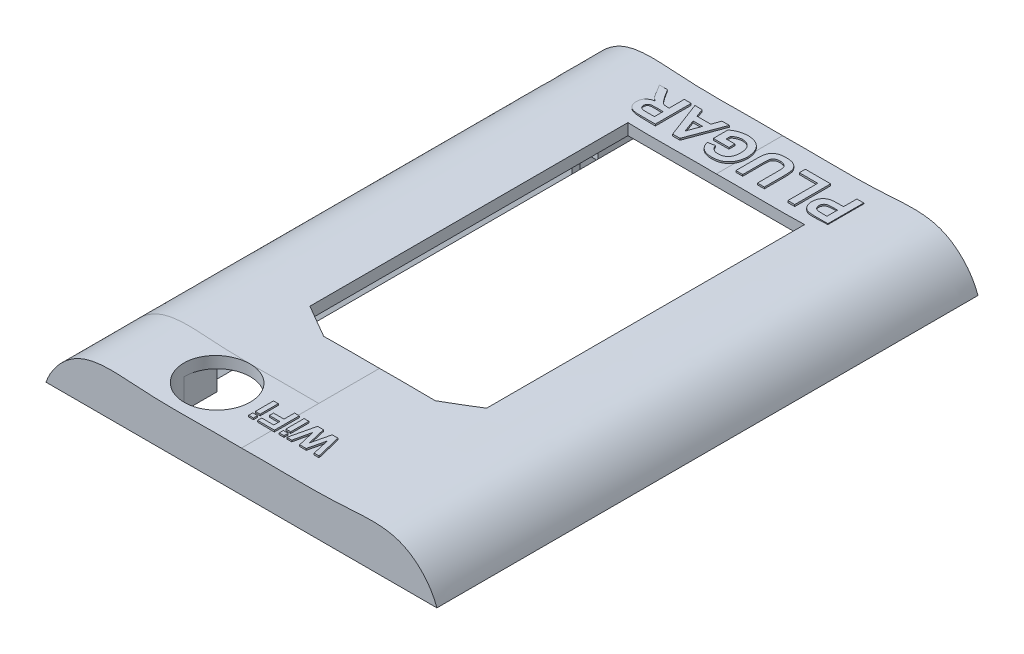
SolidWorks part; units mm, degrees
other "Câmera1"
ref_plane "Plano frontal" through (0, 0, 0) normal (0, 0, 1) x (1, 0, 0)
ref_plane "Plano superior" through (0, 0, 0) normal (0, 1, 0) x (1, 0, 0)
ref_plane "Plano direito" through (0, 0, 0) normal (1, 0, 0) x (0, 0, -1)
sketch "Forma Principal" plane through (0, 0, 0) normal (0, 0, 1) x (1, 0, 0)
  line L0 (20.4, -12.0302) -> (20.4, -9.6302)
  line L1 (0, 6.1527) -> (0, -15) construction
  line L2 (-20.4, -15) -> (-18.9151, -13.5151)
  line L3 (-35.4, -15) -> (-20.4, -15)
  line L4 (-20.4, -9.6302) -> (20.4, -9.6302)
  line L5 (-18.9151, -13.5151) -> (-20.4, -12.0302)
  line L6 (-20.4, -12.0302) -> (-20.4, -9.6302)
  line L7 (18.9151, -13.5151) -> (20.4, -12.0302)
  line L8 (35.4, -15) -> (20.4, -15)
  line L9 (20.4, -15) -> (18.9151, -13.5151)
  spline S0 degree 3 poles (-35.4, -15) (-34.3652, -12.0385) (-29.3659, -6.48) (-20.6106, -7.4076) (-11.0454, -7.778) (-4.641, -7.544) (0, -7.6302) knots 0 0 0 0 0.248558 0.508028 0.637571 1 1 1 1
  spline S1 degree 3 poles (35.4, -15) (34.3652, -12.0385) (29.3659, -6.48) (20.6106, -7.4076) (11.0454, -7.778) (4.641, -7.544) (0, -7.6302) knots 0 0 0 0 0.248558 0.508028 0.637571 1 1 1 1
  point P0 (0, 0)
  point P25 (0, -9.6302)
  dimension "D6" = 10
  dimension "D7" = 19
  dimension "D9" = 4
  dimension "D10" = 2
  dimension "D12" = 2.2
  dimension "D13" = 2
  dimension "D8" = 14
  dimension "D3" = 38.793
  dimension "D2" = 20.4
  dimension "D4" = 4
  dimension "D5" = 15
  dimension "D11" = 2
  dimension "D14" = 2.1
  dimension "D15" = 2.1
  dimension "D16" = 45
  dimension "D17" = 15
  dimension "D18" = 7
  dimension "D19" = 2.4
extrude "Corpo da Tampa" add sketch "Forma Principal" along normal blind 84
sketch "Esboço4" plane through (0, 0, 84) normal (0, 0, 1) x (1, 0, 0)
  line L1 (0, -7.6302) -> (0, -15) construction
  line L2 (-35.4, -15) -> (35.4, -15)
  spline S0 degree 3 poles (-35.4, -15) (-34.3652, -12.0385) (-29.3659, -6.48) (-20.6106, -7.4076) (-11.0454, -7.778) (-4.641, -7.544) (0, -7.6302) knots 0 0 0 0 0.248558 0.508028 0.637571 1 1 1 1
  spline S1 degree 3 poles (35.4, -15) (34.3652, -12.0385) (29.3659, -6.48) (20.6106, -7.4076) (11.0454, -7.778) (4.641, -7.544) (0, -7.6302) knots 0 0 0 0 0.248558 0.508028 0.637571 1 1 1 1
  dimension "D7" = 4
  dimension "D6" = 38.793
  dimension "D2" = 7.3698
  dimension "D3" = 7.3698
  dimension "D4" = 7.5698
  dimension "D5" = 6.8931
  dimension "D8" = 10
  dimension "D9" = 4
  dimension "D10" = 7.3698
  dimension "D14" = 7
  dimension "D18" = 7
extrude "Tampa Superior" add sketch "Esboço4" along normal blind 14
sketch "Esboço6" plane through (20.4, 0, 0) normal (-1, 0, 0) x (0, 0, 1)
  line L0 (84, -12.0302) -> (0, -12.0302) construction
  line L1 (17.75, -12.0302) -> (16.25, -12.0302)
  line L2 (17.75, -12.0302) -> (17.75, -15)
  line L3 (17.75, -15) -> (16.25, -15)
  line L4 (16.25, -12.0302) -> (16.25, -15)
  line L8 (13, -12.0302) -> (0, -12.0302)
  line L9 (13, -12.0302) -> (13, -15)
  line L10 (13, -15) -> (0, -15)
  line L11 (0, -12.0302) -> (0, -15)
  line L12 (84, -15) -> (0, -15) construction
  dimension "D1" = 1.5
  dimension "D2" = 16.25
  dimension "D3" = 13
extrude "Gancho Tampa" cut sketch "Esboço6" along normal blind 1.5 draft 45 draft outward yes
sketch "Esboço Antena" plane through (0, -15, 0) normal (0, -1, 0) x (1, 0, 0)
  line L3 (-6.4, 90) -> (-6.4, 84)
  line L4 (-20.4, 84) -> (20.4, 84) construction
  line L5 (-6.4, 84) -> (-18.4, 84)
  line L6 (-18.4, 84) -> (-18.4, 90)
  line L8 (-20.4, 84) -> (-20.4, 0) construction
  arc A0 (-6.4, 90) -> (-18.4, 90) centre (-12.4, 90) ccw
  dimension "D1" = 6
  dimension "D2" = 6
  dimension "D3" = 8
sketch "Furo" plane through (0, -9.6302, 0) normal (0, -1, 0) x (1, 0, 0)
  line L0 (0, 98) -> (0, 0) construction
  line L1 (-35.4, 98) -> (35.4, 98) construction
  line L2 (-16, 69.5936) -> (-10.1, 73)
  line L3 (-10.1, 73) -> (10.1, 73)
  line L4 (-16, 69.5936) -> (-16, 12)
  line L5 (-16, 12) -> (16, 12)
  line L6 (16, 69.5936) -> (16, 12)
  line L7 (-16, 73) -> (16, 12) construction
  line L8 (-16, 12) -> (16, 73) construction
  line L9 (10.1, 73) -> (16, 69.5936)
  line L12 (-35.4, 0) -> (0, 0) construction
  point P5 (0, 42.5)
  dimension "D1" = 12
  dimension "D2" = 61
  dimension "D3" = 32
  dimension "D4" = 5.9
  dimension "D5" = 30
  dimension "D6" = 5.9
  dimension "D7" = 30
extrude "Furo Furo" cut sketch "Furo" against normal blind 10
mirror "Gancho Espelho" about plane through (0, 0, 0) normal (1, 0, 0) of "Gancho Tampa"
extrude "Furo Interno Antena" cut sketch "Esboço Antena" against normal up to surface (5.3698 mm away) up to face at (0, -9.6302, 51.5312)
sketch "Furo Antena" plane through (0, -9.6302, 0) normal (0, -1, 0) x (1, 0, 0)
  circle A0 centre (-12.4, 90) radius 6
extrude "Corte Antena" cut sketch "Furo Antena" against normal through all
sketch "Escrito" plane through (0, -9.6302, 0) normal (0, -1, 0) x (1, 0, 0)
  line L0 (-20.4, 3.5) -> (20.4, 3.5) construction
  line L1 (-20.4, 84) -> (-20.4, 0) construction
  line L2 (20.4, 84) -> (20.4, 0) construction
  line L3 (-20.4, 0) -> (20.4, 0) construction
  line L6 (-6.4, 84) -> (20.4, 84) construction
  line L8 (20.4, 88) -> (-4.6, 88) construction
  line L10 (20.4, 84) -> (20.4, 17.75) construction
  text T0 "PLUGAR" font "Arial" height 6.5
  text T2 "WiFi" font "Arial" height 4.5
  dimension "D1" = 3.5
  dimension "D3" = 0.9059
  dimension "D4" = 10.7726
  dimension "D7" = 25
  dimension "D8" = 0.7452
  dimension "D9" = 17.2307
  dimension "D10" = 4
extrude "Texto" add sketch "Escrito" against normal blind 2.3
